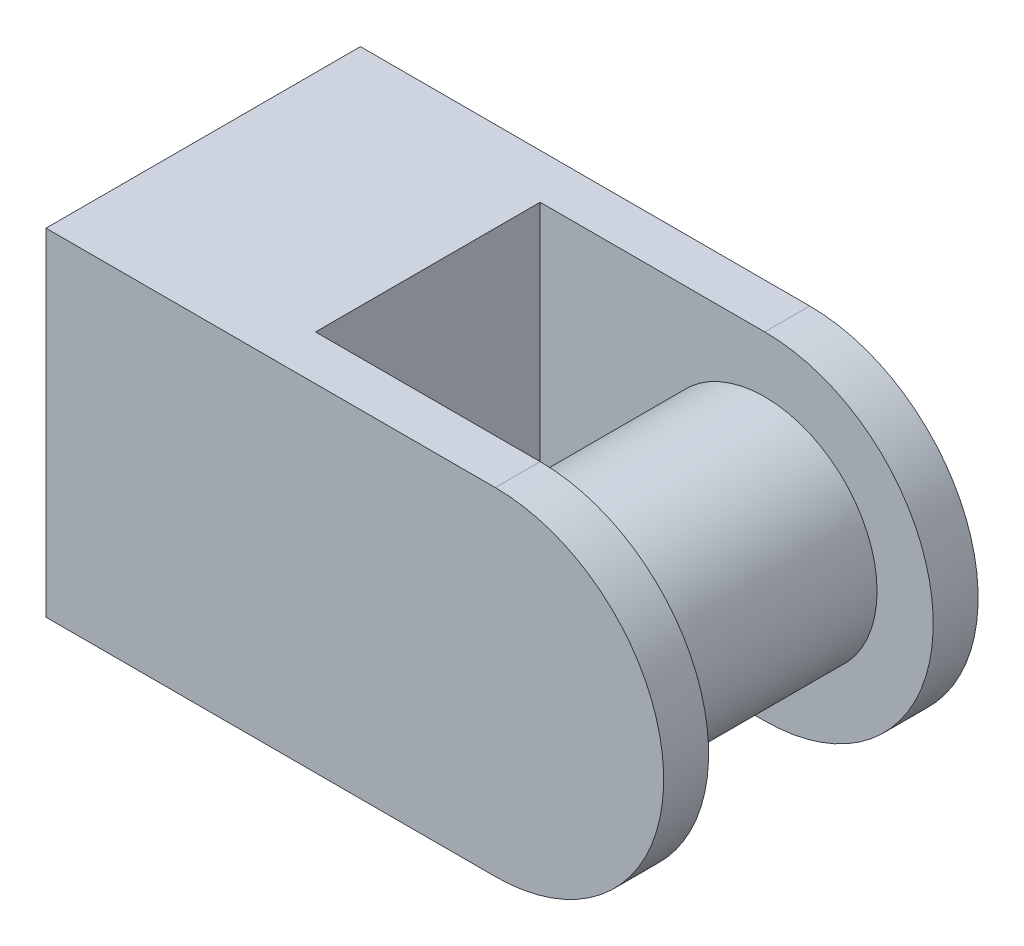
SolidWorks part; units mm, degrees
material "201 Annealed Stainless Steel (SS)"
ref_plane "Front Plane" through (0, 0, 0) normal (0, 0, 1) x (1, 0, 0)
ref_plane "Top Plane" through (0, 0, 0) normal (0, 1, 0) x (1, 0, 0)
ref_plane "Right Plane" through (0, 0, 0) normal (1, 0, 0) x (0, 0, -1)
sketch "Sketch1" plane through (0, 0, 0) normal (1, 0, 0) x (0, 0, -1)
  line L1 (-70, 75) -> (70, 75)
  line L2 (-70, 75) -> (-70, -75)
  line L3 (-70, -75) -> (70, -75)
  line L4 (70, 75) -> (70, -75)
  line L5 (-70, 75) -> (70, -75) construction
  line L6 (-70, -75) -> (70, 75) construction
  point P0 (0, 0)
  dimension "D1" = 150
  dimension "D2" = 140
extrude "Boss-Extrude1" add sketch "Sketch1" along normal blind 240
sketch "Sketch2" plane through (240, 0, 0) normal (1, 0, 0) x (0, 0, -1)
  circle A0 centre (0, 0) radius 65
  dimension "D1" = 130
extrude "Boss-Extrude2" add sketch "Sketch2" along normal blind 50
sketch "Sketch3" plane through (290, 0, 0) normal (1, 0, 0) x (0, 0, -1)
  circle A0 centre (0, 0) radius 70
  dimension "D1" = 140
extrude "Boss-Extrude3" add sketch "Sketch3" along normal blind 10
sketch "Sketch4" plane through (0, 0, 0) normal (0, 0, 1) x (1, 0, 0)
  line L0 (0, -75) -> (16.2188, -158.4383)
  line L1 (0, 75) -> (0, -75) construction
  line L2 (170.0448, -145) -> (170.0448, -75)
  line L3 (240, -75) -> (0, -75) construction
  line L5 (0, -75) -> (170.0448, -75)
  arc A0 (16.2188, -158.4383) -> (170.0448, -145) centre (92.5448, -145) ccw
  circle A1 centre (92.5448, -145) radius 50
  dimension "D1" = 155
  dimension "D2" = 100
  dimension "D3" = 191
  dimension "D4" = 85
  dimension "D5" = 70
extrude "Boss-Extrude4" add sketch "Sketch4" along normal mid plane 160
fillet "Fillet1" radius 10 3 edges at (85.0224, -75, 70) (240, 0, -65) (85.0224, -75, -70)
sketch "Sketch5" plane through (300, 0, 0) normal (1, 0, 0) x (0, 0, -1)
  circle A0 centre (0, 0) radius 65
  dimension "D1" = 130
extrude "Boss-Extrude5" add sketch "Sketch5" along normal blind 20
sketch "Sketch6" plane through (0, 0, 0) normal (0, 0, 1) x (1, 0, 0)
  line L0 (520, 75) -> (320, 75)
  line L1 (320, 75) -> (320, -75)
  line L2 (320, -75) -> (520, -75)
  line L3 (320, -65) -> (320, 65) construction
  arc A0 (520, -75) -> (520, 75) centre (520, 0) ccw
  dimension "D1" = 150
  dimension "D2" = 200
extrude "Boss-Extrude7" add sketch "Sketch6" along normal mid plane 140
sketch "Sketch8" plane through (0, 0, 0) normal (0, 0, 1) x (1, 0, 0)
  line L0 (520, 75) -> (420, 75)
  line L1 (520, 75) -> (320, 75) construction
  line L2 (420, 75) -> (420, -75)
  line L3 (320, -75) -> (520, -75) construction
  line L4 (420, -75) -> (520, -75)
  arc A0 (520, -75) -> (520, 75) centre (520, 0) ccw construction
  arc A1 (520, -75) -> (520, 75) centre (520, 0) ccw
extrude "Cut-Extrude1" cut sketch "Sketch8" against normal mid plane 100
sketch "Sketch9" plane through (0, 0, -50) normal (0, 0, 1) x (1, 0, 0)
  circle A0 centre (520, 0) radius 50
  dimension "D1" = 100
extrude "Boss-Extrude8" add sketch "Sketch9" along normal blind 100
sketch "Sketch10" plane through (320, 0, 0) normal (-1, 0, 0) x (0, 0, 1)
  line L1 (-174.3157, 128.8522) -> (197.652, 128.8522)
  line L2 (-174.3157, 128.8522) -> (-174.3157, -308.1745)
  line L3 (-174.3157, -308.1745) -> (197.652, -308.1745)
  line L4 (197.652, 128.8522) -> (197.652, -308.1745)
  line L5 (11.6682, -308.1745) -> (11.6682, 128.8522) construction
  line L6 (-174.3157, -89.6612) -> (197.652, -89.6612) construction
  point P0 (11.6682, -89.6612)
extrude "Cut-Extrude2" cut sketch "Sketch10" along normal through all
sketch "Sketch11" plane through (0, 0, 0) normal (0, 1, 0) x (1, 0, 0)
  line L0 (76.5412, 0) -> (320, 0) construction
  line L1 (320, -70) -> (320, 70) construction
  point P4 (0, 0)
